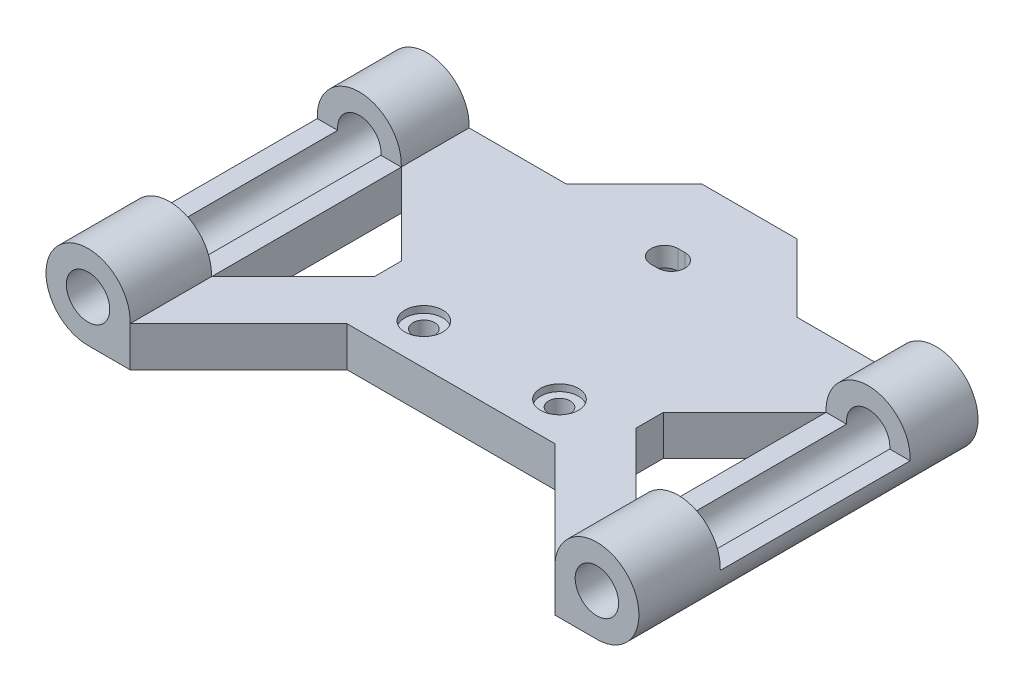
SolidWorks part; units mm, degrees
ref_plane "前视基准面" through (0, 0, 0) normal (0, 0, 1) x (1, 0, 0)
ref_plane "上视基准面" through (0, 0, 0) normal (0, 1, 0) x (1, 0, 0)
ref_plane "右视基准面" through (0, 0, 0) normal (1, 0, 0) x (0, 0, -1)
other "Configuration Table"
sketch "草图1" plane through (0, 0, 0) normal (0, 0, 1) x (1, 0, 0)
  line L0 (-46.5078, 2.4292) -> (-8.9878, 2.4292)
  line L1 (-43.4117, 5.3742) -> (-12.0839, 5.3742)
  line L3 (-37.4778, 5.3742) -> (-18.0178, 5.3742) construction
  circle A0 centre (-46.5078, 5.5292) radius 1.6
  circle A1 centre (-8.9878, 5.5292) radius 1.6
  circle A2 centre (-46.5078, 5.5292) radius 3.1
  circle A3 centre (-8.9878, 5.5292) radius 3.1
  circle A5 centre (-8.9878, 5.5292) radius 1.525 construction
  circle A6 centre (-46.5078, 5.5292) radius 1.525 construction
  point P2 (0, 0)
  point P5 (-47.4849, 5.8567)
  dimension "D1" = 3.2
  dimension "D2" = 1.5
extrude "凸台-拉伸1" add sketch "草图1" along normal blind 25 contours A2 A0 | A3 L1 A2 L0 | A3 A1 region at (-27.7478, 3.8683, 0) region at (-48.6378, 7.6592, 0) region at (-11.0639, 3.3466, 0)
sketch "草图2" plane through (0, 5.3742, 0) normal (0, 1, 0) x (1, 0, 0)
  line L0 (-19.2478, 0) -> (-24.2478, 5)
  line L1 (-43.4117, 0) -> (-12.0839, 0) construction
  line L2 (-24.2478, 5) -> (-31.2478, 5)
  line L4 (-31.2478, 5) -> (-36.2478, 0)
  line L6 (-27.7478, 17.7449) -> (-27.7478, -46.0927) construction
  line L9 (-43.4078, -25) -> (-43.4078, 0) construction
  line L10 (-12.0878, 0) -> (-12.0878, -25) construction
  line L11 (-36.2478, 0) -> (-19.2478, 0)
  dimension "D1" = 5
  dimension "D2" = 7
  dimension "D3" = 45
extrude "凸台-拉伸2" add sketch "草图2" against normal up to surface (2.945 mm away) up to face at (-27.7478, 2.4292, 12.5)
sketch "草图3" plane through (0, 5.3742, 0) normal (0, 1, 0) x (1, 0, 0)
  line L0 (-27.9978, -1) -> (-27.4978, -1) construction
  line L1 (-27.9978, 0) -> (-27.4978, 0)
  line L2 (-27.9978, -2) -> (-27.4978, -2)
  line L3 (-24.2478, 5) -> (-31.2478, 5) construction
  arc A0 (-27.9978, 0) -> (-27.9978, -2) centre (-27.9978, -1) ccw
  arc A1 (-27.4978, -2) -> (-27.4978, 0) centre (-27.4978, -1) ccw
  point P2 (-27.7478, -1)
  point P10 (-27.7478, 5)
  dimension "D1" = 1
  dimension "D2" = 0.5
  dimension "15" = 6
extrude "切除-拉伸1" cut sketch "草图3" against normal through all
sketch "草图5" plane through (0, 2.4292, 0) normal (0, -1, 0) x (-1, 0, 0)
  line L17 (29.8649, -1) -> (28.6813, 1.05)
  line L18 (28.6813, 1.05) -> (26.3142, 1.05)
  line L19 (26.3142, 1.05) -> (25.1306, -1)
  line L20 (25.1306, -1) -> (26.3142, -3.05)
  line L21 (26.3142, -3.05) -> (28.6813, -3.05)
  line L22 (28.6813, -3.05) -> (29.8649, -1)
  line L23 (30.3649, -1) -> (29.1813, 1.05)
  line L24 (29.1813, 1.05) -> (26.8142, 1.05)
  line L25 (26.8142, 1.05) -> (25.6306, -1)
  line L26 (25.6306, -1) -> (26.8142, -3.05)
  line L27 (26.8142, -3.05) -> (29.1813, -3.05)
  line L28 (29.1813, -3.05) -> (30.3649, -1)
  circle A4 centre (27.4978, -1) radius 2.05 construction
  arc A5 (27.4978, 0) -> (27.4978, -2) centre (27.4978, -1) ccw construction
  circle A6 centre (27.9978, -1) radius 2.05 construction
  arc A7 (27.9978, -2) -> (27.9978, 0) centre (27.9978, -1) ccw construction
  line M17 (27.4978, 0) -> (27.9978, 0)
  arc M18 (27.9978, 0) -> (27.9978, -2) centre (27.9978, -1) cw
  line M19 (27.9978, -2) -> (27.4978, -2)
  arc M20 (27.4978, -2) -> (27.4978, 0) centre (27.4978, -1) cw
  dimension "D1" = 4.1
extrude "切除-拉伸4" cut sketch "草图5" against normal blind 1.5 contours L26 L25 L18 L19 L20 L21 | L25 L26 L21 L22 L17 L18 M20 M17 M18 M19 | L27 L28 L23 L24 L17 L22 region at (-29.2221, 2.4292, 1.9955) region at (-29.3115, 2.4292, -0.0472) region at (-26.184, 2.4292, -0.0472)
sketch "草图6" plane through (0, 5.3742, 0) normal (0, 1, 0) x (1, 0, 0)
  line L1 (-27.7478, -17.7348) -> (-27.7478, -33.5164) construction
  line L2 (-43.4117, -25) -> (-12.0839, -25) construction
  circle A0 centre (-32.7478, -14) radius 0.8
  circle A1 centre (-22.7478, -14) radius 0.8
  arc A3 (-27.4978, -2) -> (-27.4978, 0) centre (-27.4978, -1) ccw construction
  point P6 (-27.7478, -25)
  dimension "D2" = 1.6
  dimension "D3" = 13
  dimension "D1" = 10
extrude "切除-拉伸5" cut sketch "草图6" against normal through all
sketch "草图7" plane through (0, 5.3742, 0) normal (0, 1, 0) x (1, 0, 0)
  line L0 (-35.4078, -17) -> (-20.0839, -17)
  line L1 (-20.0839, -17) -> (-12.0839, -25)
  line L2 (-43.4078, -25) -> (-35.4078, -17)
  line L3 (-43.4117, -25) -> (-12.0839, -25) construction
  line L4 (-43.4078, -5) -> (-35.4078, -13)
  line L5 (-43.4078, -25) -> (-43.4078, 0) construction
  line L6 (-35.4078, -13) -> (-35.4078, -17)
  line L7 (-12.0878, -5) -> (-20.0839, -12.9961)
  line L8 (-12.0878, 0) -> (-12.0878, -25) construction
  line L9 (-20.0839, -12.9961) -> (-20.0839, -17)
  line L10 (-43.4078, -19) -> (-35.4078, -11)
  line L11 (-20.0839, -11.0039) -> (-12.0878, -19)
  line L12 (-27.7478, 9.0219) -> (-27.7478, -36.5602) construction
  line L13 (-24.2478, 5) -> (-31.2478, 5) construction
  line L14 (-43.4117, 0) -> (-36.2478, 0) construction
  line L15 (-43.4078, -5) -> (-43.4078, -19)
  line L16 (-12.0878, -5) -> (-12.0878, -19)
  line L17 (-37.4078, -11) -> (-37.4078, -13)
  line L18 (-18.0878, -11) -> (-18.0878, -13)
  circle A0 centre (-32.7478, -14) radius 0.8 construction
  point P26 (-27.7478, 5)
  line M18 (-43.4117, -25) -> (-12.0839, -25)
  dimension "D1" = 45
  dimension "D2" = 6
  dimension "D3" = 3
  dimension "D4" = 45
  dimension "D5" = 45
  dimension "D6" = 5
  dimension "D7" = 6
extrude "切除-拉伸6" cut sketch "草图7" against normal through all contours L4 L15 L10 L6 | L12 L0 L2 M18 | L0 L12 M18 | L16 L7 L9 L11 region at (-33.8065, 5.3742, 21.4574) region at (-21.6872, 5.3742, 21.4573) region at (-41.1578, 5.3742, 12) region at (-14.3378, 5.3742, 12)
sketch "草图9" plane through (-12.0878, 0, 0) normal (-1, 0, 0) x (0, 0, 1)
  line L0 (25, 3.9292) -> (25, 7.1292) construction
  line L1 (25, 3.9292) -> (25, 7.1292)
  line L2 (0, 8.6292) -> (0, 2.4292) construction
  line L3 (25, 3.9292) -> (0, 3.9292)
  line L4 (25, 3.9292) -> (25, 8.6292)
  line L5 (25, 8.6292) -> (0, 8.6292)
  line L6 (0, 3.9292) -> (0, 8.6292)
  line L7 (25, 8.6292) -> (0, 8.6292) construction
  line L8 (5, 5.3742) -> (19, 5.3742) construction
  line L9 (5, 5.3742) -> (19, 5.3742)
  line L12 (19, 5.3742) -> (5, 5.3742)
  line L13 (5, 5.3742) -> (5, 2.4292)
  line L14 (5, 2.4292) -> (19, 2.4292)
  line L15 (19, 2.4292) -> (19, 5.3742)
  line L17 (5, 8.6292) -> (5, 2.4292)
  line L18 (5, 2.4292) -> (19, 2.4292)
  line L19 (19, 2.4292) -> (19, 8.6292)
  line M5 (19, 5.3742) -> (5, 5.3742)
  dimension "D1" = 0
extrude "切除-拉伸9" cut sketch "草图9" against normal through all contours L19 L5 L17 M5 region at (-12.0878, 7.0017, 12)
ref_plane "基准面1" through (-27.7478, 0, 0) normal (1, 0, 0) x (0, 0, -1)
mirror "镜向1" about plane through (-27.7478, 0, 0) normal (1, 0, 0) of "切除-拉伸9"
sketch "草图10" plane through (0, 5.3742, 0) normal (0, 1, 0) x (1, 0, 0)
  circle A0 centre (-22.7478, -14) radius 1.4
  circle A1 centre (-32.7478, -14) radius 1.4
  circle A2 centre (-22.7478, -14) radius 0.8 construction
  circle A3 centre (-32.7478, -14) radius 0.8 construction
  dimension "D1" = 2.8
extrude "切除-拉伸11" cut sketch "草图10" against normal blind 0.5
